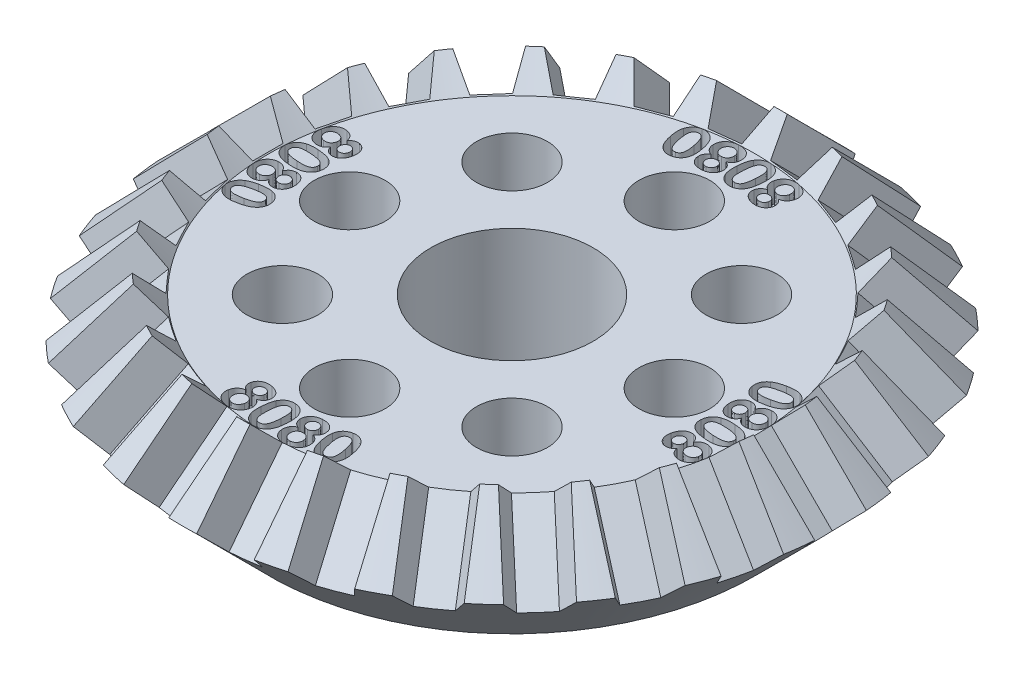
SolidWorks part; units mm, degrees
ref_plane "Front Plane" through (0, 0, 0) normal (0, 0, 1) x (1, 0, 0)
ref_plane "Top Plane" through (0, 0, 0) normal (0, 1, 0) x (1, 0, 0)
ref_plane "Right Plane" through (0, 0, 0) normal (1, 0, 0) x (0, 0, -1)
sketch "Sketch2" plane through (0, 0, 0) normal (0, 0, 1) x (1, 0, 0)
  line L6 (0, 0) -> (0, 6)
  line L7 (0, 0) -> (-12, 0)
  line L8 (0, 6) -> (-12, 6)
  line L9 (-12, 0) -> (-16.2426, 4.2426)
  line L14 (-16.2426, 4.2426) -> (-13.2426, 7.2426)
  line L15 (-12, 6) -> (-13.2426, 7.2426)
  dimension "D1" = 6
  dimension "D2" = 12
  dimension "D3" = 12
  dimension "D4" = 45
  dimension "D5" = 6
revolve "Revolve4" add sketch "Sketch2" angle 360 about L6
sketch "Sketch3" plane through (0, 0, 0) normal (0, 0, 1) x (1, 0, 0)
  line L0 (0, 0) -> (0, 20.4853) construction
  line L1 (0, 20.4853) -> (0, -16.6359) construction
  line L2 (0, 20.4853) -> (-22.6315, -2.1462) construction
  line L3 (-13.2426, 7.2426) -> (-16.2426, 4.2426) construction
ref_plane "Plane1" through (-6, -6, 0) normal (-0.7071, -0.7071, 0) x (0, 0, 1)
sketch "Sketch4" plane through (-6, -6, 0) normal (-0.7071, -0.7071, 0) x (0, 0, 1)
  line L0 (0, 9.4379) -> (0, 20.3385) construction
  line L1 (0, 0) -> (0, 14.4853) construction
  line L8 (-0.7471, 12.7911) -> (0.7471, 12.7911)
  line L9 (0.7471, 12.7911) -> (1.4119, 14.8882)
  line L10 (1.4119, 14.8882) -> (-1.4119, 14.8882)
  line L11 (-0.7471, 12.7911) -> (-1.4119, 14.8882)
  point P9 (0, 12.845)
  point P10 (0, 12.7911)
  point P11 (0, 14.0042)
  point P12 (0, 14.8882)
  point P13 (0, 17.9558)
  point P14 (0, 14.0042)
  point P15 (0, 17.9558)
  point P16 (0, 0)
  point P17 (0.7471, 12.7911)
  point P18 (0, 0)
  point P19 (1.4119, 14.8882)
sketch "Sketch5" plane through (0, 6, 0) normal (0, 1, 0) x (1, 0, 0)
  line L0 (0, 0) -> (0, -8)
  circle A0 centre (0, 0) radius 4
  circle A1 centre (0, -8) radius 1.75
  dimension "D1" = 8
  dimension "D3" = 3.5
  dimension "D2" = 8
extrude "Cut-Extrude3" cut sketch "Sketch5" against normal blind 10 contours A0 region at (-2.7484, 6, -2.7484)
extrude "Cut-Extrude4" cut sketch "Sketch5<3>" against normal blind 10 contours A1
sketch "Sketch5<3>" plane through (0, 6, 0) normal (0, 1, 0) x (1, 0, 0) same geometry as "Sketch5"
pattern_circular "CirPattern3" count 8 over 360 about axis through (0, 0, 0) along (0, 1, 0) of "Cut-Extrude4"
sketch "Sketch6" plane through (0, 6, 0) normal (0, 1, 0) x (1, 0, 0)
  text T0 "8080" font "Arial Rounded MT Bold" height 2
extrude "Cut-Extrude10" cut sketch "Sketch6" against normal blind 1
pattern_circular "CirPattern10" count 4 over 360 about axis through (0, 0, 0) along (0, 1, 0) of "Cut-Extrude10" reverse direction yes
extrude "Cut-Extrude11" cut sketch "Sketch4" against normal blind 10 contours L10 L11 L8 L9
pattern_circular "CirPattern12" count 26 over 360 about axis through (0, 0, 0) along (0, 1, 0) of "Cut-Extrude11" reverse direction yes
